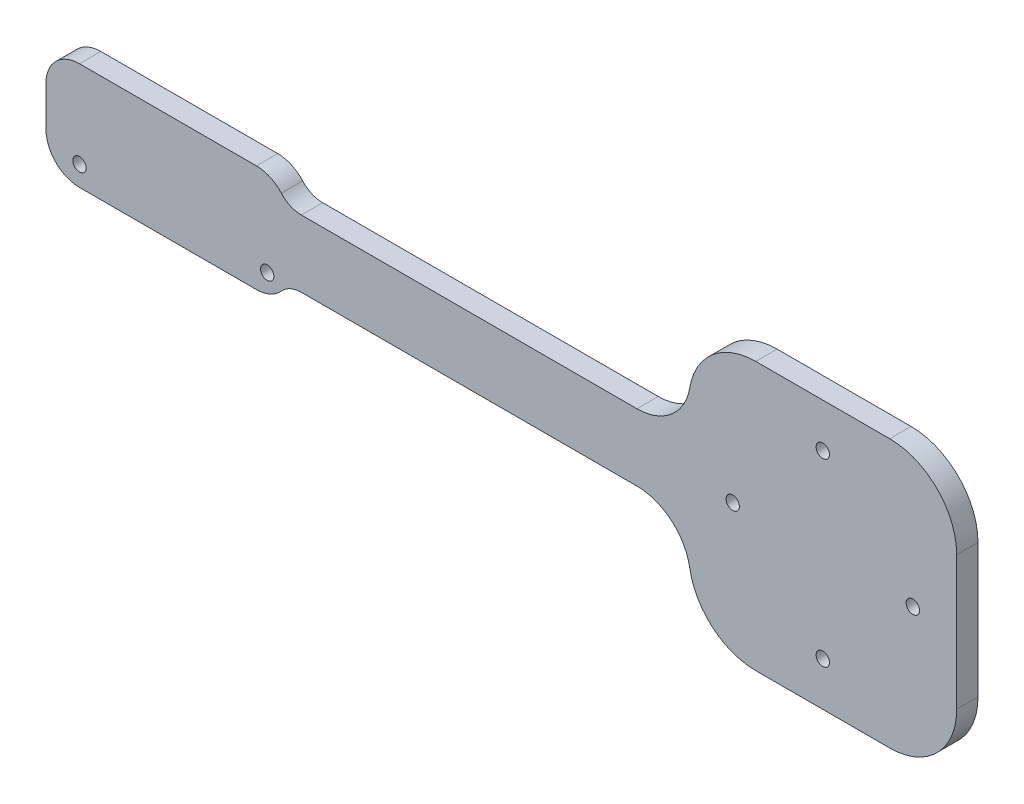
SolidWorks part; units mm, degrees
ref_plane "Front Plane" through (0, 0, 0) normal (0, 0, 1) x (1, 0, 0)
ref_plane "Top Plane" through (0, 0, 0) normal (0, 1, 0) x (1, 0, 0)
ref_plane "Right Plane" through (0, 0, 0) normal (1, 0, 0) x (0, 0, -1)
sketch "Sketch1" plane through (0, 0, 0) normal (0, 0, 1) x (1, 0, 0)
  line L1 (30, 20) -> (70, 20)
  line L2 (30, 20) -> (30, -20)
  line L3 (30, -20) -> (70, -20)
  line L4 (70, 20) -> (70, -20)
  line L5 (30, 20) -> (70, -20) construction
  line L6 (30, -20) -> (70, 20) construction
  point P0 (50, 0)
  dimension "D1" = 40
  dimension "D2" = 30
extrude "Boss-Extrude1" add sketch "Sketch1" along normal blind 3.18
sketch "Sketch2" plane through (30, 0, 0) normal (-1, 0, 0) x (0, 0, 1)
  line L0 (3.18, 20) -> (3.18, -20) construction
  line L1 (3.18, -5) -> (0, -5)
  line L2 (3.18, -5) -> (3.18, 5)
  line L3 (3.18, 5) -> (0, 5)
  line L4 (0, -5) -> (0, 5)
  line L5 (3.18, -5) -> (0, 5) construction
  line L6 (3.18, 5) -> (0, -5) construction
  line L7 (3.18, 20) -> (0, 20) construction
  point P0 (1.59, 0)
  dimension "D1" = 3.18
  dimension "D2" = 10
  dimension "D3" = 15
extrude "Boss-Extrude2" add sketch "Sketch2" along normal blind 60
sketch "Sketch3" plane through (-30, 0, 0) normal (-1, 0, 0) x (0, 0, 1)
  line L1 (3.18, -8) -> (0, -8)
  line L2 (3.18, -8) -> (3.18, 8)
  line L3 (3.18, 8) -> (0, 8)
  line L4 (0, -8) -> (0, 8)
  line L5 (3.18, -8) -> (0, 8) construction
  line L6 (3.18, 8) -> (0, -8) construction
  line L9 (3.18, -5) -> (3.18, 5) construction
  line L13 (0, 5) -> (0, -5) construction
  point P0 (1.59, 0)
  point P11 (0, 0)
  dimension "D1" = 16
  dimension "D2" = 3.18
extrude "Boss-Extrude3" add sketch "Sketch3" along normal blind 36
fillet "Fillet1" radius 10 4 edges at (30, 20, 1.59) (70, 20, 1.59) (70, -20, 1.59) (30, -20, 1.59)
fillet "Fillet2" radius 8 2 edges at (30, 5, 1.59) (30, -5, 1.59)
fillet "Fillet3" radius 5 4 edges at (-30, 8, 1.59) (-66, 8, 1.59) (-66, -8, 1.59) (-30, -8, 1.59)
fillet "Fillet4" radius 4 2 edges at (-30, -5, 1.59) (-30, 5, 1.59)
sketch "Sketch7" plane through (0, 0, 3.18) normal (0, 0, 1) x (1, 0, 0)
  line L0 (70, -10) -> (70, 10) construction
  line L1 (60, 20) -> (40, 20) construction
  circle A0 centre (63.45, 0) radius 1
  circle A1 centre (36.55, 0) radius 1
  circle A2 centre (50, 13.45) radius 1
  circle A3 centre (50, -13.45) radius 1
  dimension "D1" = 2
  dimension "D2" = 26.9
  dimension "D3" = 6.55
  dimension "D4" = 6.55
  dimension "D5" = 26.9
  dimension "D6" = 20
extrude "Cut-Extrude2" cut sketch "Sketch7" against normal blind 3.18
sketch "Sketch8" plane through (0, 0, 3.18) normal (0, 0, 1) x (1, 0, 0)
  line L0 (-66, -3) -> (-66, 3) construction
  line L2 (-61, -8) -> (-34.5826, -8) construction
  circle A0 centre (-32.97, -5) radius 1
  circle A1 centre (-61, -5) radius 1
  dimension "D1" = 2
  dimension "D3" = 5
  dimension "D4" = 3
  dimension "D2" = 28.03
extrude "Cut-Extrude3" cut sketch "Sketch8" against normal blind 3.18
